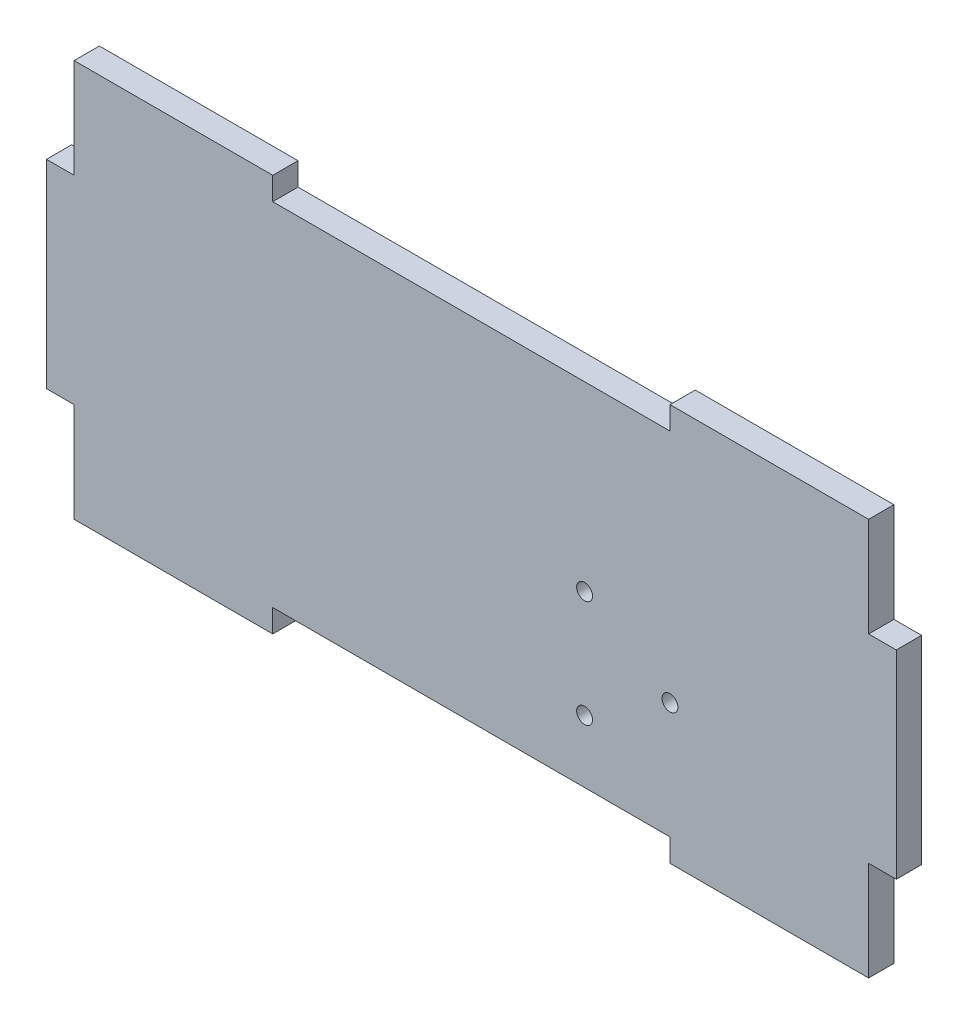
SolidWorks part; units mm, degrees
ref_plane "Front Plane" through (0, 0, 0) normal (0, 0, 1) x (1, 0, 0)
ref_plane "Top Plane" through (0, 0, 0) normal (0, 1, 0) x (1, 0, 0)
ref_plane "Right Plane" through (0, 0, 0) normal (1, 0, 0) x (0, 0, -1)
sketch "Sketch1" plane through (0, 0, 0) normal (0, 0, 1) x (1, 0, 0)
  line L1 (-100, 50) -> (100, 50)
  line L2 (-100, 50) -> (-100, -50)
  line L3 (-100, -50) -> (100, -50)
  line L4 (100, 50) -> (100, -50)
  line L5 (-100, 50) -> (100, -50) construction
  line L6 (-100, -50) -> (100, 50) construction
  point P0 (0, 0)
  dimension "D1" = 100
  dimension "D2" = 200
extrude "Boss-Extrude1" add sketch "Sketch1" along normal blind 6.36
sketch "Sketch2" [suppressed] plane through (0, 0, 3.36) normal (0, 0, 1) x (1, 0, 0)
  line L0 (50, 50) -> (-50, 50) construction
  line L1 (-25, 50) -> (25, 50)
  line L2 (-25, 50) -> (-25, 53.36)
  line L3 (-25, 53.36) -> (25, 53.36)
  line L4 (25, 50) -> (25, 53.36)
  line L5 (0, 0) -> (0, 53.36) construction
  line L6 (0, 0) -> (50, 0) construction
  line L7 (50, -50) -> (50, 50) construction
  dimension "D1" = 6.36
  dimension "D2" = 50
sketch "Sketch8" plane through (0, 0, 0) normal (0, 0, -1) x (-1, 0, 0)
  line L0 (0, 0) -> (0, 50) construction
  line L1 (-100, 50) -> (100, 50) construction
  line L2 (0, 0) -> (100, 0) construction
  line L3 (100, 50) -> (100, -50) construction
  line L5 (-50, 50) -> (50, 50)
  line L6 (-50, 50) -> (-50, 56.96)
  line L7 (-50, 56.96) -> (50, 56.96)
  line L8 (50, 50) -> (50, 56.96)
  dimension "D2" = 6.96
  dimension "D1" = 100
extrude "Boss-Extrude4" [suppressed] add sketch "Sketch8" against normal blind 6.36
mirror "Mirror4" [suppressed] about plane through (0, 0, 0) normal (0, 1, 0)
sketch "Sketch9" plane through (0, 0, 0) normal (0, 0, -1) x (-1, 0, 0)
  line L0 (0, 0) -> (100, 0) construction
  line L1 (100, 50) -> (100, -50) construction
  line L3 (100, 25) -> (106.96, 25)
  line L4 (100, 25) -> (100, -25)
  line L5 (100, -25) -> (106.96, -25)
  line L6 (106.96, 25) -> (106.96, -25)
  dimension "D1" = 50
  dimension "D2" = 6.96
extrude "Boss-Extrude5" add sketch "Sketch9" against normal blind 6.36
mirror "Mirror5" about plane through (0, 0, 0) normal (1, 0, 0) of "Boss-Extrude5"
sketch "Sketch10" plane through (0, 0, 6.36) normal (0, 0, 1) x (1, 0, 0)
  line L0 (0, 0) -> (0, 50) construction
  line L1 (100, 50) -> (-100, 50) construction
  line L3 (-50, 50) -> (50, 50)
  line L4 (-50, 50) -> (-50, 44.24)
  line L5 (-50, 44.24) -> (50, 44.24)
  line L6 (50, 50) -> (50, 44.24)
  dimension "D1" = 5.76
  dimension "D2" = 100
extrude "Cut-Extrude1" cut sketch "Sketch10" against normal through all and the other way through all
mirror "Mirror6" about plane through (0, 0, 0) normal (0, 1, 0) of "Cut-Extrude1"
sketch "Sketch11" plane through (0, 0, 6.36) normal (0, 0, 1) x (1, 0, 0)
  line L0 (0, 0) -> (100, 0) construction
  line L1 (100, -50) -> (100, -25) construction
  line L3 (100, 25) -> (94.24, 25)
  line L4 (100, 25) -> (100, -25)
  line L5 (100, -25) -> (94.24, -25)
  line L6 (94.24, 25) -> (94.24, -25)
  dimension "D2" = 50
  dimension "D1" = 5.76
extrude "Cut-Extrude2" [suppressed] cut sketch "Sketch11" against normal through all and the other way through all
mirror "Mirror7" [suppressed] about plane through (0, 0, 0) normal (1, 0, 0)
sketch "Sketch12" plane through (0, 0, 6.36) normal (0, 0, 1) x (1, 0, 0)
  line L0 (-100, -25) -> (-100, -50) construction
  line L1 (-100, -50) -> (-50, -50) construction
  line L2 (-75, -25) -> (-75, 23.3) construction
  line L3 (-22.6, 8) -> (-22.6, -19.9) construction
  circle A0 centre (-75, -25) radius 1.6
  circle A1 centre (-73.4, 23.3) radius 1.6
  circle A2 centre (-22.6, -19.9) radius 1.6
  circle A3 centre (-22.6, 8) radius 1.6
  dimension "D1" = 3.2
  dimension "D2" = 25
  dimension "D3" = 25
  dimension "D5" = 48.3
  dimension "D7" = 5.1
  dimension "D9" = 50.8
  dimension "D10" = 27.9
extrude "arduino holes" [suppressed] cut sketch "Sketch12" against normal through all and the other way through all
sketch "Sketch13" plane through (0, 0, 6.36) normal (0, 0, 1) x (1, 0, 0)
  line L0 (50, -15) -> (-18.2265, -15) construction
  line L1 (100, -50) -> (100, -25) construction
  line L2 (50, -50) -> (100, -50) construction
  circle A0 centre (50, -15) radius 2
  circle A1 centre (28.5, -1.5) radius 2
  circle A2 centre (28.5, -28.5) radius 2
  dimension "D1" = 4
  dimension "D2" = 27
  dimension "D3" = 21.5
  dimension "D4" = 50
  dimension "D5" = 35
extrude "battery holes" cut sketch "Sketch13" against normal blind 10
equation "\"Sheet Thickness\"= 6.36mm"
equation "\"Height\"= 100mm"
equation "\"Length\"= 200mm"
equation "\"Width\"= 100mm"
equation "\"D1@Boss-Extrude1\"=\"Sheet Thickness\""
equation "\"D1@Sketch2\"=\"Sheet Thickness\""
equation "\"D2@Sketch2\"=\"Height\"/2"
equation "\"Kerf\"= .60mm"
equation "\"D2@Sketch9\"=\"Sheet Thickness\"+\"Kerf\""
equation "\"D1@Sketch9\"    = \"Height\"/2"
equation "\"D2@Sketch8\"=\"Sheet Thickness\"+\"Kerf\""
equation "\"D1@Sketch10\"=\"Sheet Thickness\"-\"Kerf\""
equation "\"D2@Sketch10\"   = \"Length\"/2"
equation "\"D1@Sketch11\"=\"Sheet Thickness\"-\"Kerf\""
equation "\"D2@Sketch11\"=\"Height\"/2"
